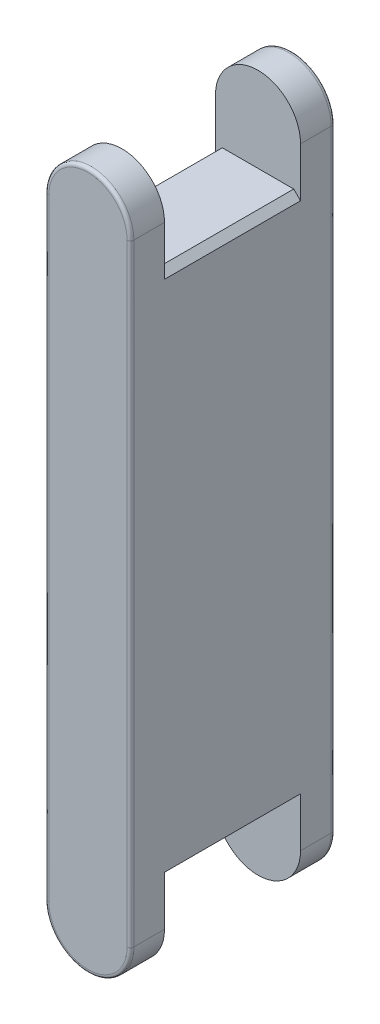
SolidWorks part; units mm, degrees
ref_plane "前视基准面" through (0, 0, 0) normal (0, 0, 1) x (1, 0, 0)
ref_plane "上视基准面" through (0, 0, 0) normal (0, 1, 0) x (1, 0, 0)
ref_plane "右视基准面" through (0, 0, 0) normal (1, 0, 0) x (0, 0, -1)
sketch "草图1" plane through (0, 0, 0) normal (0, 0, 1) x (1, 0, 0)
  line L0 (0, 0) -> (0, 180) construction
  line L1 (-12.5, 0) -> (-12.5, 180)
  line L2 (12.5, 0) -> (12.5, 180)
  arc A0 (-12.5, 0) -> (12.5, 0) centre (0, 0) ccw
  arc A1 (12.5, 180) -> (-12.5, 180) centre (0, 180) ccw
  point P3 (0, 90)
  point P8 (-73.5594, 136.0509)
  dimension "D1" = 12.5
  dimension "D2" = 180
extrude "凸台-拉伸1" add sketch "草图1" along normal mid plane 60
sketch "草图2" plane through (0, 0, 0) normal (0, 0, 1) x (1, 0, 0)
  line L3 (-23.3538, 12.5) -> (23.3538, 12.5)
  line L4 (-23.3538, 12.5) -> (-23.3538, -12.5)
  line L5 (-23.3538, -12.5) -> (23.3538, -12.5)
  line L6 (23.3538, 12.5) -> (23.3538, -12.5)
  line L7 (-23.3538, 12.5) -> (23.3538, -12.5) construction
  line L8 (-23.3538, -12.5) -> (23.3538, 12.5) construction
  line L9 (-27.3414, 167.5) -> (27.3414, 167.5)
  line L10 (-27.3414, 167.5) -> (-27.3414, 192.5)
  line L11 (-27.3414, 192.5) -> (27.3414, 192.5)
  line L12 (27.3414, 167.5) -> (27.3414, 192.5)
  line L13 (-27.3414, 167.5) -> (27.3414, 192.5) construction
  line L14 (-27.3414, 192.5) -> (27.3414, 167.5) construction
  arc A2 (-12.5, 0) -> (12.5, 0) centre (0, 0) ccw construction
  arc A3 (12.5, 180) -> (-12.5, 180) centre (0, 180) ccw construction
  point P0 (0, 0)
  point P12 (0, 180)
extrude "切除-拉伸1" cut sketch "草图2" against normal mid plane 40
chamfer "倒角1" distance 2 angle 45 4 edges at (-12.5, 167.5, 0) (-12.5, 12.5, 0) (12.5, 12.5, 0) (12.5, 167.5, 0)
fillet "圆角1" radius 1 8 edges at (-12.5, 90, 30) (0, 192.5, 30) (12.5, 90, 30) (0, -12.5, 30) (12.5, 90, -30) (0, 192.5, -30) (-12.5, 90, -30) (0, -12.5, -30) curvature continuous yes
